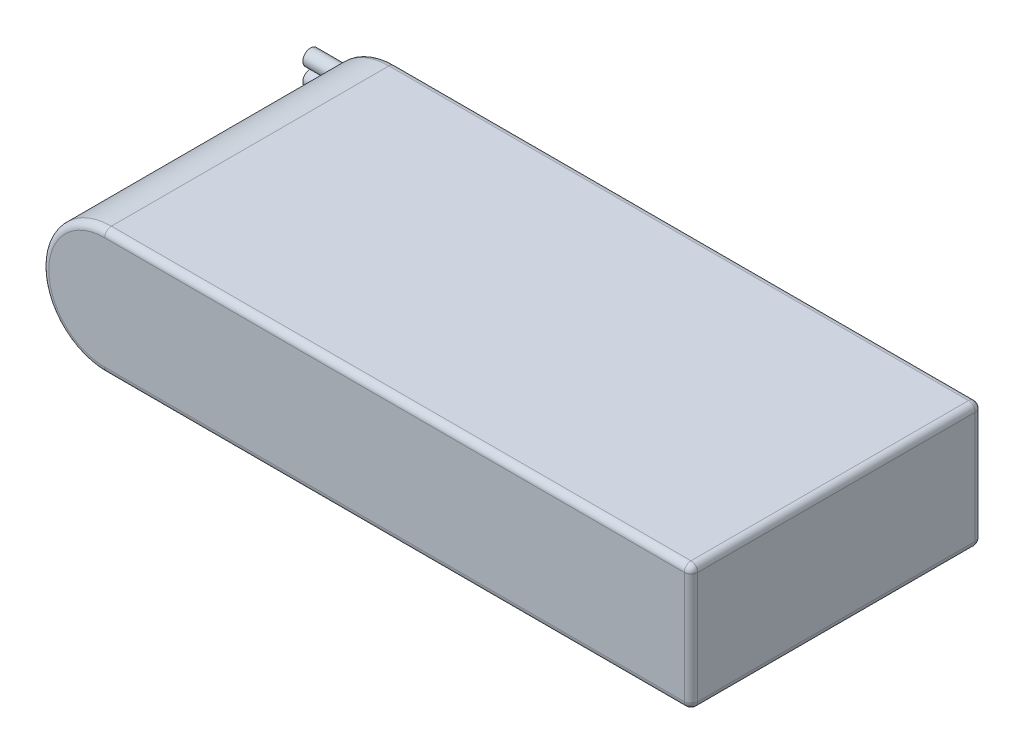
SolidWorks part; units mm, degrees
ref_plane "Front Plane" through (0, 0, 0) normal (0, 0, 1) x (1, 0, 0)
ref_plane "Top Plane" through (0, 0, 0) normal (0, 1, 0) x (1, 0, 0)
ref_plane "Right Plane" through (0, 0, 0) normal (1, 0, 0) x (0, 0, -1)
sketch "Sketch1" plane through (0, 0, 0) normal (0, 0, 1) x (1, 0, 0)
  line L0 (-29.718, 0) -> (29.718, 0) construction
  line L1 (-29.718, 7.112) -> (29.718, 7.112)
  line L2 (-29.718, -7.112) -> (29.718, -7.112)
  arc A0 (-29.718, 7.112) -> (-29.718, -7.112) centre (-29.718, 0) ccw
  arc A1 (29.718, -7.112) -> (29.718, 7.112) centre (29.718, 0) ccw
  point P2 (0, 0)
  point P8 (-36.83, 0)
  point P9 (36.83, 0)
  dimension "D1" = 14.224
  dimension "D2" = 73.66
extrude "Boss-Extrude1" add sketch "Sketch1" along normal mid plane 33.02
sketch "Sketch2" plane through (0, 0, 16.51) normal (0, 0, 1) x (1, 0, 0)
  line L1 (29.718, 7.112) -> (36.83, 7.112)
  line L2 (29.718, 7.112) -> (29.718, -7.112)
  line L3 (29.718, -7.112) -> (36.83, -7.112)
  line L4 (36.83, 7.112) -> (36.83, -7.112)
  arc A0 (29.718, -7.112) -> (29.718, 7.112) centre (29.718, 0) ccw construction
extrude "Boss-Extrude2" add sketch "Sketch2" against normal up to surface (33.02 mm away) up to face at (0, 0, -16.51)
sketch "Sketch3" plane through (0, 0, 0) normal (1, 0, 0) x (0, 0, -1)
  line L0 (15.24, 0) -> (0, 0) construction
  line L1 (15.24, -4.064) -> (15.24, -2.032) construction
  line L2 (15.24, -2.032) -> (15.24, 0) construction
  line L3 (15.24, 0) -> (15.24, 2.032) construction
  line L4 (15.24, 2.032) -> (15.24, 4.064) construction
  line L5 (16.51, 7.112) -> (16.51, -7.112) construction
  circle A0 centre (15.24, 4.064) radius 0.889
  circle A1 centre (15.24, 2.032) radius 0.889
  circle A2 centre (15.24, 0) radius 0.889
  circle A3 centre (15.24, -2.032) radius 0.889
  circle A4 centre (15.24, -4.064) radius 0.889
  dimension "D1" = 1.778
  dimension "D2" = 1.27
  dimension "D3" = 2.032
extrude "Boss-Extrude3" add sketch "Sketch3" against normal blind 38.1
fillet "Fillet1" radius 0.762 10 edges at (-36.83, 0, -16.51) (3.556, -7.112, -16.51) (3.556, 7.112, -16.51) (36.83, 7.112, 0) (36.83, 0, -16.51) (36.83, -7.112, 0) (-36.83, 0, 16.51) (3.556, 7.112, 16.51) (36.83, 0, 16.51) (3.556, -7.112, 16.51)
